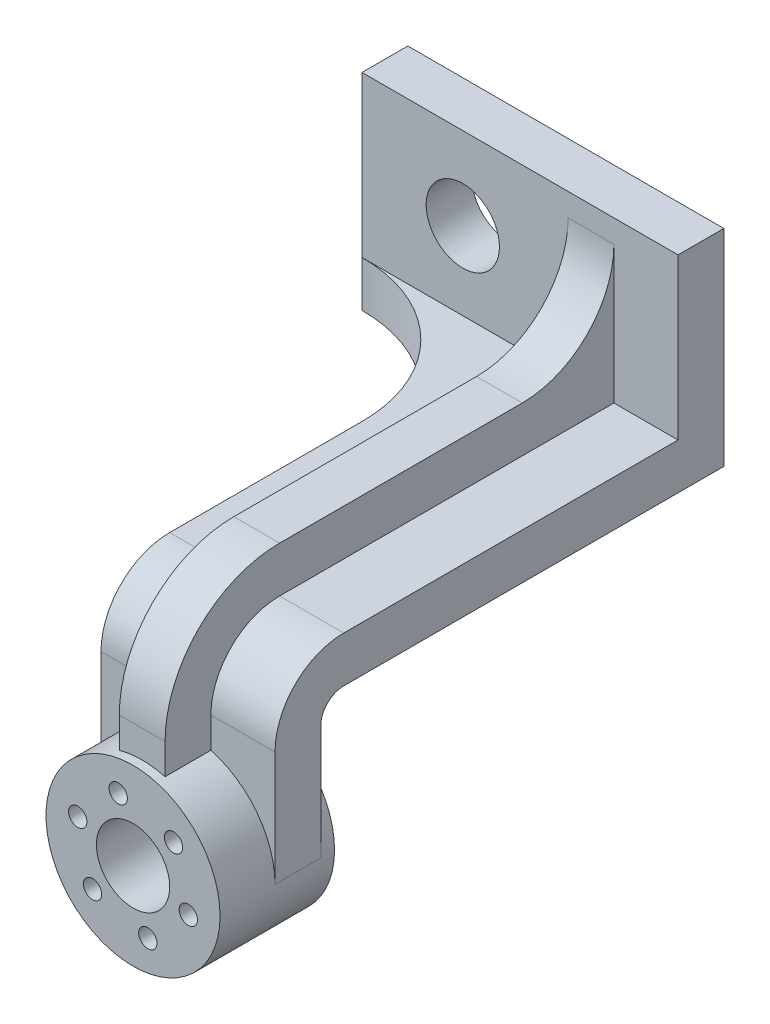
SolidWorks part; units mm, degrees
ref_plane "Front Plane" through (0, 0, 0) normal (0, 0, 1) x (1, 0, 0)
ref_plane "Top Plane" through (0, 0, 0) normal (0, 1, 0) x (1, 0, 0)
ref_plane "Right Plane" through (0, 0, 0) normal (1, 0, 0) x (0, 0, -1)
sketch "Sketch1" plane through (0, 0, 0) normal (0, 0, 1) x (1, 0, 0)
  line L0 (0, 0) -> (-43449.185, 0) construction
  line L1 (0, 0) -> (0, -43449.185) construction
  line L2 (0, 0) -> (0, -30)
  line L3 (0, 0) -> (-69, 0)
  line L4 (0, 0) -> (0, 45)
  line L5 (0, 45) -> (-69, 45)
  line L6 (-69, 0) -> (-69, 45)
  line L9 (0, 10) -> (-69, 10)
  line L11 (-38, -30) -> (-38, 0)
  line L12 (-19, -30) -> (-3.5526, -14.5526) construction
  line L13 (-19, -30) -> (0, -30) construction
  line L14 (-38, 0) -> (-38, 10)
  circle A0 centre (-47, 27) radius 8
  circle A1 centre (-19, -30) radius 19
  circle A2 centre (-19, -30) radius 12.5 construction
  circle A3 centre (-19, -30) radius 8
  circle A4 centre (-10.1612, -21.1612) radius 2
  circle A5 centre (-6.9259, -33.2352) radius 2
  circle A6 centre (-15.7648, -42.0741) radius 2
  circle A7 centre (-27.8388, -38.8388) radius 2
  circle A8 centre (-31.0741, -26.7648) radius 2
  circle A9 centre (-22.2352, -17.9259) radius 2
  point P36 (-19, -30)
  dimension "D3" = 16
  dimension "D7" = 38
  dimension "D8" = 25
  dimension "D9" = 16
  dimension "D12" = 4
  dimension "D1" = 69
  dimension "D2" = 45
  dimension "D4" = 22
  dimension "D5" = 18
  dimension "D6" = 10
  dimension "D10" = 75
  dimension "D11" = 45
  dimension "D13" = 6
extrude "Boss-Extrude1" add sketch "Sketch1" against normal blind 10 contours L9 L4 L5 L6 A0 region at (-33.3648, 27.5454, 0)
extrude "Boss-Extrude3" add sketch "Sketch1<4>" along normal blind 88 and the other way blind 10 contours L14 L3 L4 L9 region at (-19, 5, 0)
sketch "Sketch1<4>" plane through (0, 0, 0) normal (0, 0, 1) x (1, 0, 0) same geometry as "Sketch1"
extrude "Boss-Extrude4" add sketch "Sketch1<5>" against normal blind 10 from surface contours A1 L2 L3 L11 region at (-19, -8.1351, 0) starting at face at (-19, 5, 88)
sketch "Sketch1<5>" plane through (0, 0, 0) normal (0, 0, 1) x (1, 0, 0) same geometry as "Sketch1"
extrude "Boss-Extrude5" add sketch "Sketch1<6>" along normal blind 25 from offset 75 contours A1 A9 A8 A7 A6 A5 A4 A3 region at (-19, -48.4626, 0)
sketch "Sketch1<6>" plane through (0, 0, 0) normal (0, 0, 1) x (1, 0, 0) same geometry as "Sketch1"
extrude "Boss-Extrude6" add sketch "Sketch1<7>" against normal blind 10 contours L3 L14 L9 L6 region at (-53.5, 5, 0)
sketch "Sketch1<7>" plane through (0, 0, 0) normal (0, 0, 1) x (1, 0, 0) same geometry as "Sketch1"
fillet "Fillet1" radius 31 1 edges at (-38, 5, 0)
fillet "Fillet3" radius 5 1 edges at (-19, 0, 78)
fillet "Fillet4" radius 15 1 edges at (-19, 10, 88)
sketch "Sketch2" plane through (0, 0, 0) normal (1, 0, 0) x (0, 0, -1)
  line L12 (-98, -13) -> (-88, -13)
  line L13 (-88, -30) -> (-88, -5) construction
  line L14 (-98, -5) -> (-98, -30)
  line L15 (0, 20) -> (-73, 20)
  line L16 (-98, -5) -> (-98, -13)
  line L17 (0, 20) -> (-73, 20)
  line L18 (0, 20) -> (0, 10)
  line L19 (-88, -11) -> (-100, -11) construction
  line L20 (0, 10) -> (-73, 10) construction
  line L21 (0, 10) -> (-73, 10)
  line L22 (-88, -13) -> (-88, -5)
  arc A4 (-73, 10) -> (-88, -5) centre (-73, -5) ccw construction
  arc A5 (-73, 20) -> (-98, -5) centre (-73, -5) ccw
  arc A6 (-73, 20) -> (-98, -5) centre (-73, -5) ccw
  arc A7 (-73, 10) -> (-88, -5) centre (-73, -5) ccw
  dimension "D2" = 2
  dimension "D1" = 10
extrude "Boss-Extrude7" add sketch "Sketch2" against normal blind 10 from offset 14 offset against normal yes
fillet "Fillet5" radius 20 1 edges at (-19, 20, 0)
